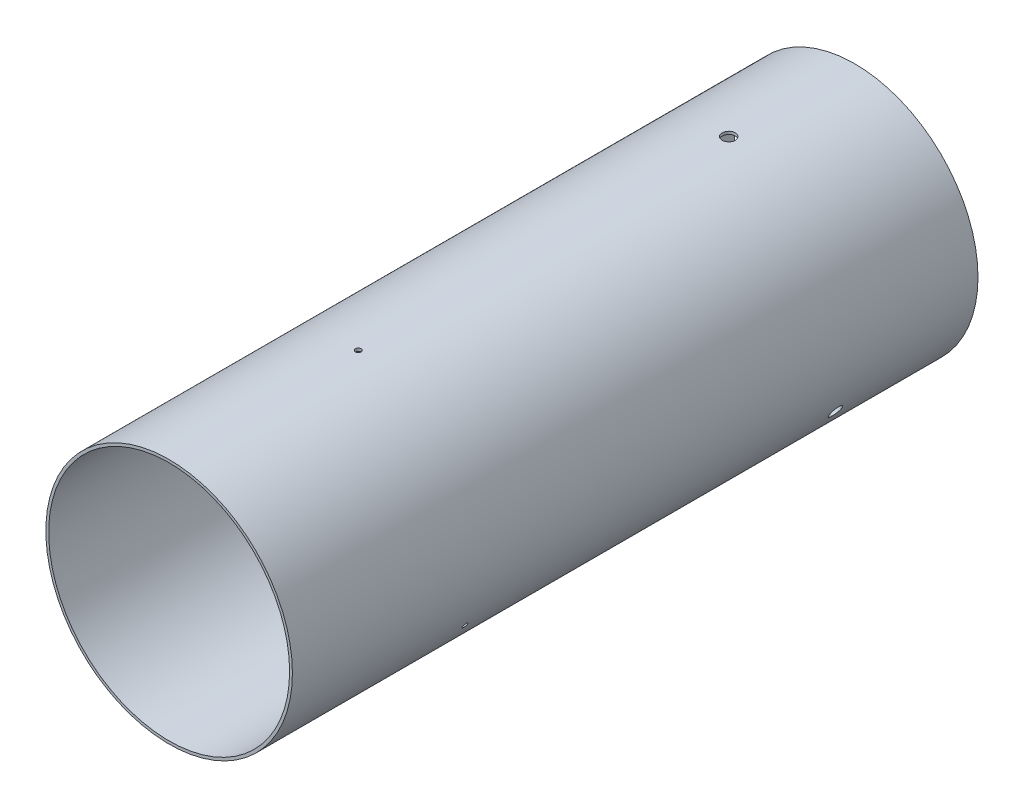
SolidWorks part; units mm, degrees
material "E-Glass Fiber"
ref_plane "Front Plane" through (0, 0, 0) normal (0, 0, 1) x (1, 0, 0)
ref_plane "Top Plane" through (0, 0, 0) normal (0, 1, 0) x (1, 0, 0)
ref_plane "Right Plane" through (0, 0, 0) normal (1, 0, 0) x (0, 0, -1)
sketch "Sketch1" plane through (0, 0, 0) normal (0, 0, 1) x (1, 0, 0)
  circle A0 centre (0, 0) radius 49.6697
  circle A1 centre (0, 0) radius 48.5394
  dimension "D1" = 99.3394
  dimension "D2" = 97.0788
extrude "Boss-Extrude1" add sketch "Sketch1" along normal blind 276.225
ref_plane "Plane1" through (0, 49.6697, 0) normal (0, 1, 0) x (1, 0, 0)
sketch "Sketch2" plane through (0, 49.6697, 0) normal (0, 1, 0) x (1, 0, 0)
  line L0 (0, 0) -> (0, -50.8) construction
  line L1 (0, -50.8) -> (0, 0) construction
  line L2 (-49.6697, -276.225) -> (49.6697, -276.225) construction
  line L3 (0, -50.8) -> (0, -200.025) construction
  line L4 (-48.5394, -276.225) -> (48.5394, -276.225) construction
  circle A0 centre (0, -50.8) radius 2.6289
  circle A2 centre (0, -200.025) radius 1.143
  dimension "D2" = 5.2578
  dimension "D6" = 2.286
  dimension "D1" = 50.8
  dimension "D3" = 276.225
  dimension "D5" = 76.2
extrude "8-32 T-Nut Holes" cut sketch "Sketch2" against normal blind 5.08
sketch "Sketch4" plane through (0, 0, 0) normal (0, 0, -1) x (-1, 0, 0)
  line L0 (0, 49.6697) -> (0, 0) construction
  line L1 (0, 0) -> (43.0152, -24.8348) construction
  circle A0 centre (0, 0) radius 49.6697 construction
  dimension "D1" = 120
ref_plane "Plane2" through (-43.0152, -24.8348, 0) normal (-0.866, -0.5, 0) x (0, 0, 1)
sketch "Sketch3" plane through (-43.0152, -24.8348, 0) normal (-0.866, -0.5, 0) x (0, 0, 1)
  line L0 (0, 0) -> (60.325, 0) construction
  line L1 (60.325, 0) -> (196.85, 0) construction
  line L4 (276.225, -49.6697) -> (276.225, 49.6697) construction
  circle A0 centre (60.325, 0) radius 2.6289
  circle A1 centre (196.85, 0) radius 1.143
  dimension "D3" = 5.2578
  dimension "D4" = 2.286
  dimension "D1" = 60.325
  dimension "D2" = 79.375
extrude "Odd_T-Nut" [suppressed] cut sketch "Sketch3" against normal blind 2.54
pattern_circular "CirPattern1" count 3 over 360 about axis through (0, 0, 276.225) along (0, 0, -1) of "8-32 T-Nut Holes"
